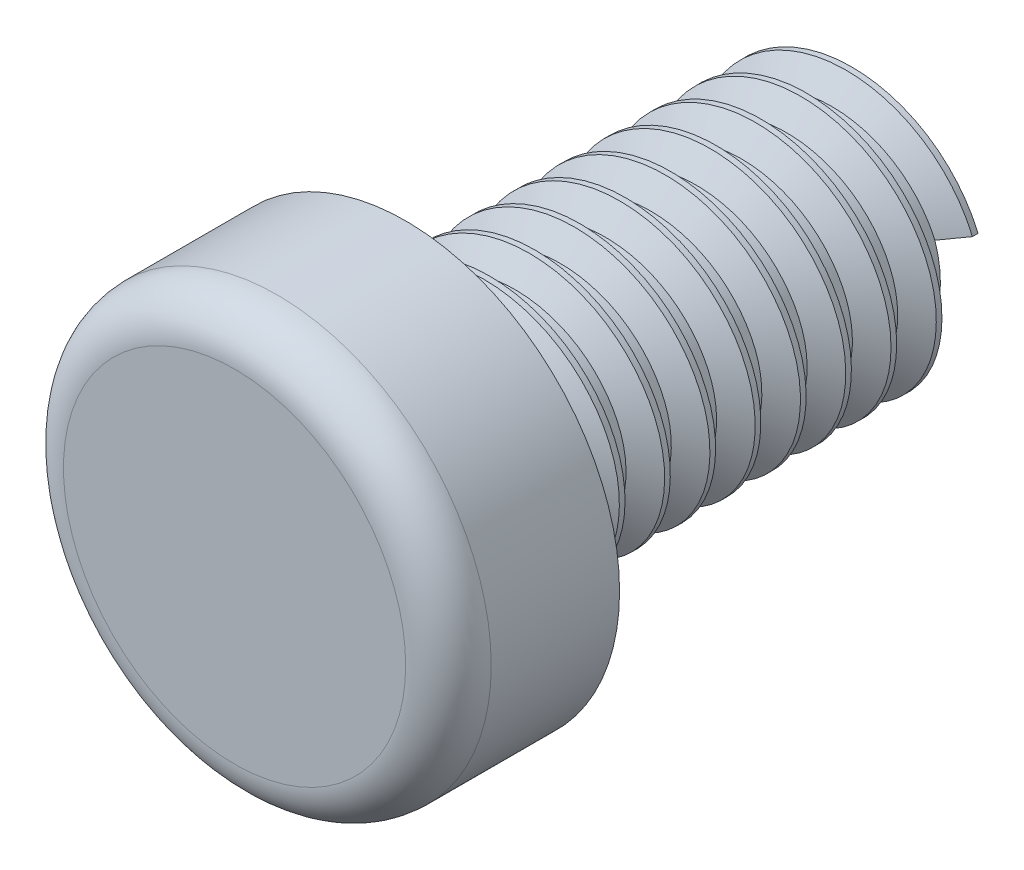
SolidWorks part; units mm, degrees
ref_plane "Front Plane" through (0, 0, 0) normal (0, 0, 1) x (1, 0, 0)
ref_plane "Top Plane" through (0, 0, 0) normal (0, 1, 0) x (1, 0, 0)
ref_plane "Right Plane" through (0, 0, 0) normal (1, 0, 0) x (0, 0, -1)
sketch "Sketch1" plane through (0, 0, 0) normal (0, 0, 1) x (1, 0, 0)
  circle A0 centre (0, 0) radius 2.5
  dimension "D1" = 5
extrude "Boss-Extrude1" add sketch "Sketch1" along normal blind 10
thread "Thread1" pitch 1.0583 start angle 0, offset 0, length 10, pitch 1.0583, diameter 5
ref_plane "Plane1" through (-2.5, 0, 10) normal (0, -1, 0) x (-1, 0, 0)
sketch "Thread Profile1" plane through (-2.5, 0, 10) normal (0, -1, 0) x (-1, 0, 0)
  line L0 (0, 0) -> (0, 1.0583) construction
  line L1 (0, 0) -> (0.5728, 0.3307)
  line L2 (0.5728, 0.3307) -> (0.5728, 0.463)
  line L3 (0.5728, 0.463) -> (0, 0.7937)
  line L4 (0.5728, 0.3969) -> (0, 0.3969) construction
  line L11 (0, 0) -> (0, 0.7937)
  point P2 (0, 0)
  dimension "Pitch" = 1.0583
  dimension "Profile_Angle" = 60
  dimension "Profile_Land" = 0.1323
  dimension "Profile_Height" = 0.5728
sketch "Sketch4" plane through (0, 0, 10) normal (0, 0, 1) x (1, 0, 0)
  circle A0 centre (0, 0) radius 5
  dimension "D1" = 10
extrude "Boss-Extrude2" add sketch "Sketch4" along normal blind 4
fillet "Fillet1" radius 1 1 edges at (5, 0, 14)
